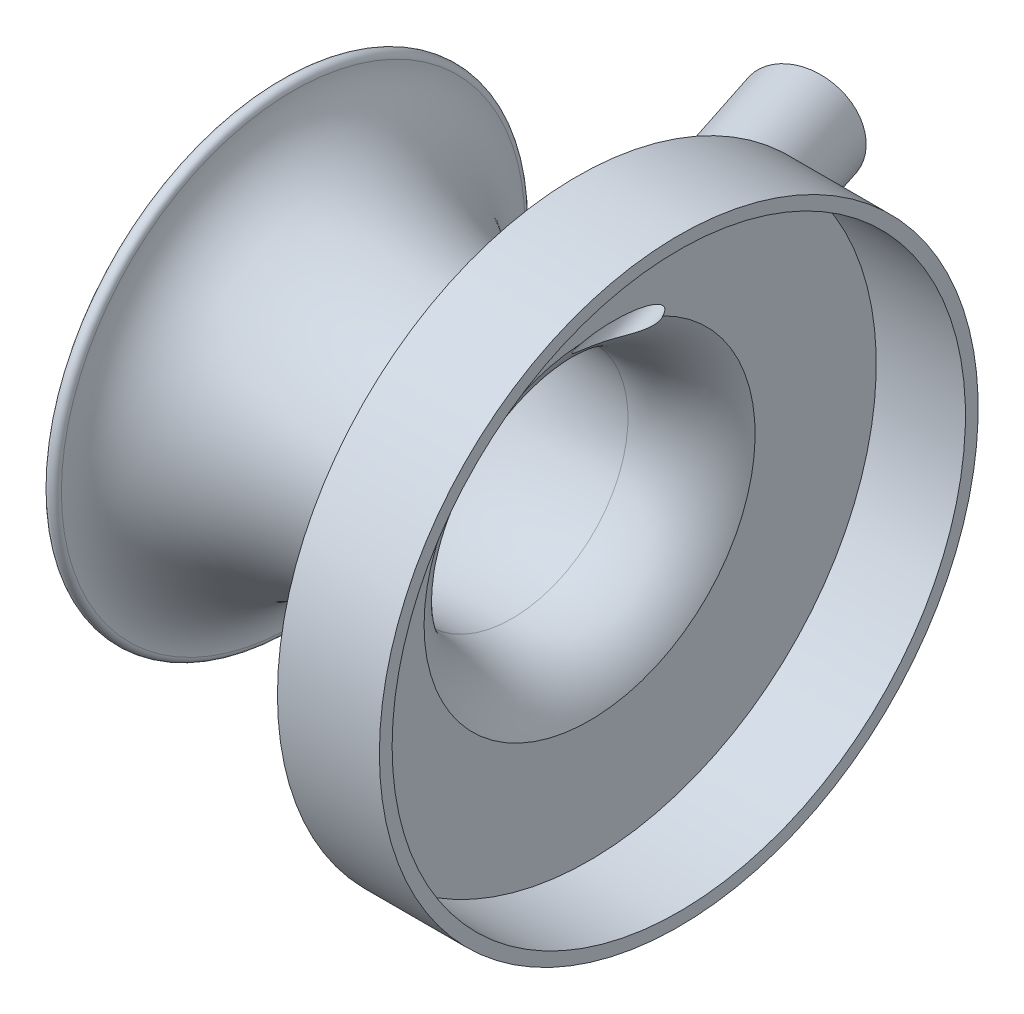
SolidWorks part; units mm, degrees
material "PVC 0.007 Plasticized"
ref_plane "Front Plane" through (0, 0, 0) normal (0, 0, 1) x (1, 0, 0)
ref_plane "Top Plane" through (0, 0, 0) normal (0, 1, 0) x (1, 0, 0)
ref_plane "Right Plane" through (0, 0, 0) normal (1, 0, 0) x (0, 0, -1)
sketch "Sketch1" plane through (0, 0, 0) normal (0, 0, 1) x (1, 0, 0)
  line L0 (-17.78, 33.4033) -> (-17.78, 57.5533)
  line L1 (-33.2264, 33.4033) -> (-8.4833, 33.4033) construction
  line L2 (-17.78, 57.5533) -> (0, 57.5533)
  line L3 (-33.2264, 0.4033) -> (55.0442, 0.4033) construction
  line L8 (-20.32, 33.9828) -> (-20.32, 60.0933)
  line L9 (-20.32, 60.0933) -> (0, 60.0933)
  line L10 (0, 60.0933) -> (0, 57.5533)
  circle A0 centre (-33.2264, 40.5033) radius 17 construction
  arc A1 (-33.2264, 23.5033) -> (-17.78, 33.4033) centre (-33.2264, 40.5033) ccw
  arc A3 (-33.2264, 26.0433) -> (-20.32, 33.9828) centre (-33.2264, 40.5033) ccw
  arc A4 (-79.4264, 46.6033) -> (-76.8864, 46.6033) centre (-78.1564, 46.6033) cw
  ellipse E0 centre (-33.2264, 46.6033) end of major axis (12.9737, 46.6033) minor radius 23.1 (-79.4264, 46.6033) -> (-33.2264, 23.5033) ccw
  ellipse E1 centre (-33.2264, 46.6033) end of major axis (12.9737, 46.6033) minor radius 23.1 construction
  spline S0 degree 1 poles (-76.8864, 46.6033) (-33.2264, 26.0433) knots 0 0 1 1 construction
  spline S1 degree 3 poles (-76.8864, 46.6033) (-76.8864, 46.0094) (-76.7711, 44.8358) (-76.0661, 42.4423) (-74.228, 39.3745) (-70.3761, 35.7484) (-64.9787, 32.4516) (-58.2618, 29.6909) (-50.5074, 27.6173) (-42.0559, 26.3331) (-36.1505, 26.0433) (-33.2264, 26.0433) knots -3.141593 -3.141593 -3.141593 -3.141593 -3.043418 -2.945243 -2.748894 -2.552544 -2.356194 -2.159845 -1.963495 -1.767146 -1.570796 -1.570796 -1.570796 -1.570796
  point P0 (-33.2264, 23.5033)
  dimension "D3" = 17
  dimension "D1" = 33.0001
  dimension "D2" = 23.1
  dimension "D4" = 33.9999
  dimension "D5" = 57.15
  dimension "D6" = 17.78
  dimension "D8" = 23.1
  dimension "D9" = 0
  dimension "D7" = 2.54
revolve "Revolve1" add sketch "Sketch1" angle 360 about L3
ref_axis "Axis1" through (0, 65.659, 0) along (0, -1, 0)
ref_plane "Plane1" through (0, 0, 0) normal (-0.309, 0, -0.9511) x (0, -1, 0)
ref_plane "Plane2" through (-13.3434, 0, -41.0666) normal (-0.309, 0, -0.9511) x (0, -1, 0)
sketch "Sketch2" plane through (-13.3434, 0, -41.0666) normal (-0.309, 0, -0.9511) x (0, -1, 0)
  line L0 (-33.0001, 18.6255) -> (-26.9006, 18.6255) construction
  circle A0 centre (-30.8893, 15.4505) radius 3.175
  circle A1 centre (-30.8893, 15.4505) radius 10.16
  circle A2 centre (-30.8893, 15.4505) radius 5.5562
  ellipse E0 centre (0, 18.6255) end of major axis (-33.0001, 18.6255) minor radius 9.0224 construction
  point P13 (0, 0)
  dimension "D1" = 6.35
  dimension "D2" = 20.32
  dimension "D3" = 11.1125
  dimension "D4" = 0
extrude "Boss-Extrude1" add sketch "Sketch2" against normal up to next separate body contours A2 A0 region at (-28.0376, 36.2884, -36.2922)
extrude "Cut-Extrude1" cut sketch "Sketch2<3>" along direction (-0.309, 0, -0.9511) on the side against the normal blind 40.64 and the other way through all contours A0 region at (-28.0376, 30.8893, -36.2922)
sketch "Sketch2<3>" plane through (-13.3434, 0, -41.0666) normal (-0.309, 0, -0.9511) x (0, -1, 0) same geometry as "Sketch2"
extrude "Boss-Extrude3" add sketch "Sketch2<4>" against normal blind 1.016 and the other way blind 25.4 contours A1 A2 region at (-28.0376, 40.7619, -36.2922)
sketch "Sketch2<4>" plane through (-13.3434, 0, -41.0666) normal (-0.309, 0, -0.9511) x (0, -1, 0) same geometry as "Sketch2"
